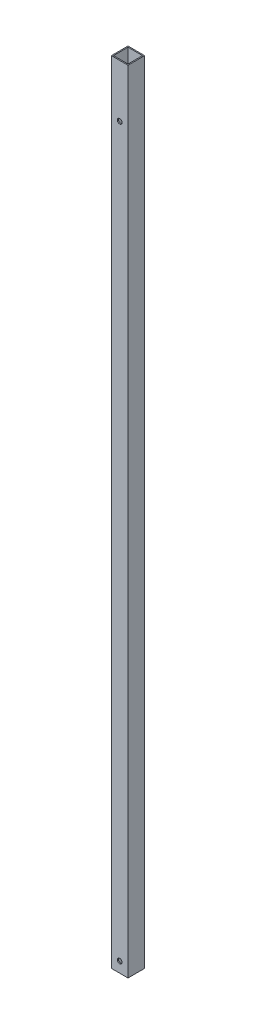
SolidWorks part; units mm, degrees
ref_plane "Front Plane" through (0, 0, 0) normal (0, 0, 1) x (1, 0, 0)
ref_plane "Top Plane" through (0, 0, 0) normal (0, 1, 0) x (1, 0, 0)
ref_plane "Right Plane" through (0, 0, 0) normal (1, 0, 0) x (0, 0, -1)
sketch "Sketch1" plane through (0, 0, 0) normal (0, 1, 0) x (1, 0, 0)
  line L0 (-6.9, -6.9) -> (-6.9, 6.9)
  line L1 (-7.9, -7.9) -> (7.9, -7.9)
  line L2 (-7.9, -7.9) -> (-7.9, 7.9)
  line L3 (-7.9, 7.9) -> (7.9, 7.9)
  line L4 (7.9, -7.9) -> (7.9, 7.9)
  line L5 (-7.9, -7.9) -> (7.9, 7.9) construction
  line L6 (-7.9, 7.9) -> (7.9, -7.9) construction
  line L7 (-6.9, 6.9) -> (6.9, 6.9)
  line L8 (6.9, -6.9) -> (6.9, 6.9)
  line L9 (-6.9, -6.9) -> (6.9, -6.9)
  point P0 (0, 0)
  dimension "D1" = 1
extrude "Boss-Extrude1" add sketch "Sketch1" along normal blind 750
sketch "Sketch3" plane through (0, 0, 7.9) normal (0, 0, 1) x (1, 0, 0)
  circle A1 centre (0, 10) radius 2.25
  circle A2 centre (0, 700) radius 2.25
  dimension "D1" = 4.5
  dimension "D2" = 4.5
  dimension "D3" = 10
extrude "Cut-Extrude1" cut sketch "Sketch3" against normal through all
